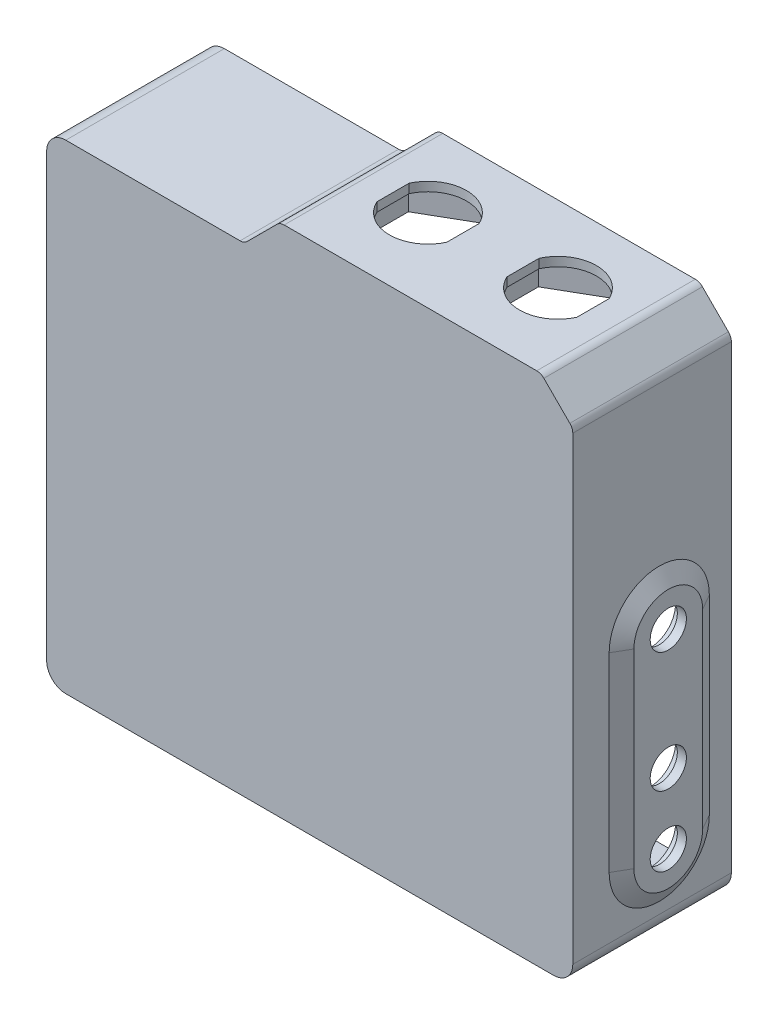
SolidWorks part; units mm, degrees
ref_plane "Front Plane" through (0, 0, 0) normal (0, 0, 1) x (1, 0, 0)
ref_plane "Top Plane" through (0, 0, 0) normal (0, 1, 0) x (1, 0, 0)
ref_plane "Right Plane" through (0, 0, 0) normal (1, 0, 0) x (0, 0, -1)
sketch "Sketch1" plane through (0, 0, 0) normal (0, 0, 1) x (1, 0, 0)
  line L9 (-68.5151, 31.874) -> (-68.5151, -49.766)
  line L10 (-31.5951, 31.874) -> (22.4049, 31.874)
  line L11 (22.4049, 31.874) -> (22.4049, -31.776)
  line L12 (22.4049, -31.776) -> (22.4049, -46.156)
  line L13 (22.4049, -46.156) -> (22.4049, -49.766)
  line L14 (-31.5951, -49.766) -> (-68.5151, -49.766)
  line L15 (22.4049, -49.766) -> (-31.5951, -49.766)
  line L16 (-31.5951, 36.874) -> (25.4049, 36.874)
  line L17 (-68.5151, 31.874) -> (-31.5951, 31.874)
  line L18 (27.4049, 34.874) -> (27.4049, -31.776)
  line L19 (27.4049, -31.776) -> (27.4049, -46.156)
  line L20 (27.4049, -46.156) -> (27.4049, -52.766)
  line L21 (25.4049, -54.766) -> (-31.5951, -54.766)
  line L22 (-31.5951, -54.766) -> (-71.5151, -54.766)
  line L23 (-73.5151, 34.874) -> (-73.5151, -52.766)
  line L24 (-71.5151, 36.874) -> (-31.5951, 36.874)
  line L25 (-31.5951, 36.874) -> (27.4049, 36.874) construction
  line L26 (27.4049, 36.874) -> (27.4049, -31.776) construction
  line L27 (27.4049, -46.156) -> (27.4049, -54.766) construction
  line L28 (27.4049, -54.766) -> (-31.5951, -54.766) construction
  line L29 (-31.5951, -54.766) -> (-73.5151, -54.766) construction
  line L30 (-73.5151, 36.874) -> (-73.5151, -54.766) construction
  line L31 (-73.5151, 36.874) -> (-31.5951, 36.874) construction
  line L32 (-71.5151, 38.674) -> (-31.5951, 38.674)
  line L33 (-31.5951, 38.674) -> (25.4049, 38.674)
  line L34 (29.2049, 34.874) -> (29.2049, -31.776)
  line L35 (29.2049, -31.776) -> (29.2049, -46.156)
  line L36 (29.2049, -46.156) -> (29.2049, -52.766)
  line L37 (25.4049, -56.566) -> (-31.5951, -56.566)
  line L38 (-31.5951, -56.566) -> (-71.5151, -56.566)
  line L39 (-75.3151, 34.874) -> (-75.3151, -52.766)
  arc A0 (25.4049, 36.874) -> (27.4049, 34.874) centre (25.4049, 34.874) cw
  arc A1 (27.4049, -52.766) -> (25.4049, -54.766) centre (25.4049, -52.766) cw
  arc A2 (-71.5151, -54.766) -> (-73.5151, -52.766) centre (-71.5151, -52.766) cw
  arc A3 (-73.5151, 34.874) -> (-71.5151, 36.874) centre (-71.5151, 34.874) cw
  arc A4 (25.4049, 38.674) -> (29.2049, 34.874) centre (25.4049, 34.874) cw
  arc A5 (29.2049, -52.766) -> (25.4049, -56.566) centre (25.4049, -52.766) cw
  arc A6 (-71.5151, -56.566) -> (-75.3151, -52.766) centre (-71.5151, -52.766) cw
  arc A7 (-75.3151, 34.874) -> (-71.5151, 38.674) centre (-71.5151, 34.874) cw
  dimension "D2" = 2
  dimension "D1" = 5
  dimension "D3" = 1.8
extrude "Boss-Extrude1" add sketch "Sketch1" along normal blind 1.5 contours L32 L33 A4 L34 L35 L36 A5 L37 L38 A6 L39 A7
sketch "Sketch2" plane through (0, 0, 1.5) normal (0, 0, 1) x (1, 0, 0)
  line L9 (-22.7084, 43.974) -> (-22.7084, 50.974)
  line L10 (-9.2084, 43.974) -> (-9.2084, 50.974)
  line L11 (3.1216, 43.974) -> (3.1216, 50.974)
  line L12 (16.6216, 43.974) -> (16.6216, 50.974)
  line L13 (18.8716, 41.674) -> (18.8716, 38.674)
  line L14 (0.8716, 41.674) -> (0.8716, 38.674)
  line L15 (-6.9584, 41.674) -> (-6.9584, 38.674)
  line L16 (-24.9584, 41.674) -> (-24.9584, 38.674)
  line L17 (-71.5151, 38.674) -> (25.4049, 38.674)
  line L18 (-22.7084, 43.974) -> (-24.9584, 43.974)
  line L19 (-24.9584, 43.974) -> (-24.9584, 41.674)
  line L20 (-9.2084, 43.974) -> (-6.9584, 43.974)
  line L21 (-6.9584, 43.974) -> (-6.9584, 41.674)
  line L22 (3.1216, 43.974) -> (0.8716, 43.974)
  line L23 (0.8716, 43.974) -> (0.8716, 41.674)
  line L24 (16.6216, 43.974) -> (18.8716, 43.974)
  line L25 (18.8716, 43.974) -> (18.8716, 41.674)
  line L26 (-22.7084, 45.774) -> (-24.9584, 45.774)
  line L27 (-9.2084, 45.774) -> (-6.9584, 45.774)
  line L28 (3.1216, 45.774) -> (0.8716, 45.774)
  line L29 (16.6216, 45.774) -> (18.8716, 45.774)
  line L30 (-24.9584, 45.774) -> (-28.9584, 45.774)
  line L31 (-28.9584, 45.774) -> (-36.0584, 38.674)
  line L32 (18.8716, 45.774) -> (22.8716, 45.774)
  line L33 (29.2049, 34.874) -> (29.2049, -52.766) construction
  line L34 (29.2049, 34.874) -> (29.2049, -52.766)
  line L35 (29.2049, 34.874) -> (29.2049, 39.4408)
  line L36 (-22.7084, 45.774) -> (-9.2084, 45.774)
  line L37 (22.8716, 45.774) -> (29.2049, 39.4408)
  line L38 (-6.9584, 45.774) -> (0.8716, 45.774)
  line L39 (3.1216, 45.774) -> (16.6216, 45.774)
  arc M10 (29.2049, 34.874) -> (25.4049, 38.674) centre (25.4049, 34.874) ccw
  line M11 (25.4049, 38.674) -> (-71.5151, 38.674)
  dimension "D1" = 1.8
  dimension "D2" = 1.8
  dimension "D3" = 1.8
  dimension "D4" = 1.8
extrude "Boss-Extrude2" add sketch "Sketch2" against normal blind 1.5 separate body contours L30 L31 L16 L19 L18 L9 L26 M11 | L36 L9 L18 L19 L16 L15 L21 L20 L10 M11 | L38 L27 L10 L20 L21 L15 L14 L23 L22 L11 L28 M11 | L39 L11 L22 L23 L14 L13 L25 L24 L12 M11 | L37 L32 L29 L12 L24 L25 L13 L35 M11 M10 region at (-28.6478, 41.8928, 1.5) region at (-15.9584, 42.0447, 1.5) region at (-3.0434, 42.561, 1.5) region at (9.8716, 42.0447, 1.5) region at (22.8246, 41.6987, 1.5)
fillet "Fillet1" radius 2 4 edges at (22.8716, 45.774, 0.75) (29.2049, 39.4408, 0.75) (-28.9584, 45.774, 0.75) (-36.0584, 38.674, 0.75)
sketch "Sketch3" plane through (0, 0, 0) normal (0, 0, -1) x (-1, 0, 0)
  line L0 (-29.2049, 38.6123) -> (-29.2049, -52.766) construction
  line L1 (-23.4574, 45.1882) -> (-28.6191, 40.0265) construction
  line L2 (-22.0432, 45.774) -> (28.1299, 45.774) construction
  line L3 (29.5442, 45.1882) -> (35.4726, 39.2598) construction
  line L4 (71.5151, 38.674) -> (36.8868, 38.674) construction
  line L5 (75.3151, 34.874) -> (75.3151, -52.766) construction
  line L6 (-25.4049, -56.566) -> (71.5151, -56.566) construction
  line L7 (-29.2049, 38.6123) -> (-29.2049, -52.766)
  line L8 (-23.4574, 45.1882) -> (-28.6191, 40.0265)
  line L9 (-22.0432, 45.774) -> (28.1299, 45.774)
  line L10 (29.5442, 45.1882) -> (35.4726, 39.2598)
  line L11 (71.5151, 38.674) -> (36.8868, 38.674)
  line L12 (75.3151, 34.874) -> (75.3151, -52.766)
  line L13 (-25.4049, -56.566) -> (71.5151, -56.566)
  line L14 (-25.4049, -54.766) -> (71.5151, -54.766)
  line L15 (73.5151, 34.874) -> (73.5151, -52.766)
  line L16 (71.5151, 36.874) -> (36.8868, 36.874)
  line L17 (28.2714, 43.9154) -> (34.1998, 37.987)
  line L18 (-22.0432, 43.974) -> (28.1299, 43.974)
  line L19 (-22.1846, 43.9154) -> (-27.3463, 38.7538)
  line L20 (-27.4049, 38.6123) -> (-27.4049, -52.766)
  arc A0 (-29.2049, -52.766) -> (-25.4049, -56.566) centre (-25.4049, -52.766) ccw construction
  arc A1 (-28.6191, 40.0265) -> (-29.2049, 38.6123) centre (-27.2049, 38.6123) ccw construction
  arc A2 (-22.0432, 45.774) -> (-23.4574, 45.1882) centre (-22.0432, 43.774) ccw construction
  arc A3 (29.5442, 45.1882) -> (28.1299, 45.774) centre (28.1299, 43.774) ccw construction
  arc A4 (35.4726, 39.2598) -> (36.8868, 38.674) centre (36.8868, 40.674) ccw construction
  arc A5 (75.3151, 34.874) -> (71.5151, 38.674) centre (71.5151, 34.874) ccw construction
  arc A6 (71.5151, -56.566) -> (75.3151, -52.766) centre (71.5151, -52.766) ccw construction
  arc A7 (-29.2049, -52.766) -> (-25.4049, -56.566) centre (-25.4049, -52.766) ccw
  arc A8 (-28.6191, 40.0265) -> (-29.2049, 38.6123) centre (-27.2049, 38.6123) ccw
  arc A9 (-22.0432, 45.774) -> (-23.4574, 45.1882) centre (-22.0432, 43.774) ccw
  arc A10 (29.5442, 45.1882) -> (28.1299, 45.774) centre (28.1299, 43.774) ccw
  arc A11 (35.4726, 39.2598) -> (36.8868, 38.674) centre (36.8868, 40.674) ccw
  arc A12 (75.3151, 34.874) -> (71.5151, 38.674) centre (71.5151, 34.874) ccw
  arc A13 (71.5151, -56.566) -> (75.3151, -52.766) centre (71.5151, -52.766) ccw
  arc A14 (71.5151, -54.766) -> (73.5151, -52.766) centre (71.5151, -52.766) ccw
  arc A15 (73.5151, 34.874) -> (71.5151, 36.874) centre (71.5151, 34.874) ccw
  arc A16 (34.1998, 37.987) -> (36.8868, 36.874) centre (36.8868, 40.674) ccw
  arc A17 (28.2714, 43.9154) -> (28.1299, 43.974) centre (28.1299, 43.774) ccw
  arc A18 (-22.0432, 43.974) -> (-22.1846, 43.9154) centre (-22.0432, 43.774) ccw
  arc A19 (-27.3463, 38.7538) -> (-27.4049, 38.6123) centre (-27.2049, 38.6123) ccw
  arc A20 (-27.4049, -52.766) -> (-25.4049, -54.766) centre (-25.4049, -52.766) ccw
  line M2 (28.1299, 45.774) -> (-22.0432, 45.774)
  arc M3 (-22.0432, 45.774) -> (-23.4574, 45.1882) centre (-22.0432, 43.774) ccw
  line M4 (-23.4574, 45.1882) -> (-28.6191, 40.0265)
  arc M5 (-28.6191, 40.0265) -> (-29.2049, 38.6123) centre (-27.2049, 38.6123) ccw
  line M6 (-29.2049, 38.6123) -> (-29.2049, -52.766)
  arc M7 (-29.2049, -52.766) -> (-25.4049, -56.566) centre (-25.4049, -52.766) ccw
  line M8 (-25.4049, -56.566) -> (71.5151, -56.566)
  arc M9 (71.5151, -56.566) -> (75.3151, -52.766) centre (71.5151, -52.766) ccw
  line M10 (75.3151, -52.766) -> (75.3151, 34.874)
  arc M11 (75.3151, 34.874) -> (71.5151, 38.674) centre (71.5151, 34.874) ccw
  line M12 (71.5151, 38.674) -> (36.8868, 38.674)
  arc M13 (36.8868, 38.674) -> (35.4726, 39.2598) centre (36.8868, 40.674) cw
  line M14 (35.4726, 39.2598) -> (29.5442, 45.1882)
  arc M15 (29.5442, 45.1882) -> (28.1299, 45.774) centre (28.1299, 43.774) ccw
  dimension "D1" = 1.8
extrude "Boss-Extrude3" add sketch "Sketch3" along normal blind 30 contours A20 L20 A19 L19 A18 L18 A17 L17 A16 L16 A15 L15 A14 L14 M15 M2 M3 M4 M5 M6 M7 M8 M9 M10 M11 M12 M13 M14 region at (27.7012, 38.8179, 0)
sketch "Sketch5" plane through (29.2049, 0, 0) normal (1, 0, 0) x (0, 0, -1)
  line L4 (-1.5, -52.766) -> (30, -52.766)
  line L5 (30, -52.766) -> (30, 38.6123)
  line L6 (30, 38.6123) -> (-1.5, 38.6123)
  line L7 (-1.5, 38.6123) -> (-1.5, -52.766)
  line L8 (-1.5, -52.766) -> (30, -52.766)
  line L9 (30, -52.766) -> (30, 38.6123)
  line L10 (30, 38.6123) -> (-1.5, 38.6123)
  line L11 (-1.5, 38.6123) -> (-1.5, -52.766)
  circle A1 centre (15.675, -40.576) radius 4.832
  circle A3 centre (15.675, -26.676) radius 4.832
  circle A5 centre (15.675, -2.776) radius 4.832
  circle A6 centre (15.675, -40.576) radius 5.032
  circle A7 centre (15.675, -26.676) radius 5.032
  circle A8 centre (15.675, -2.776) radius 5.032
  dimension "D1" = 0
  dimension "D2" = 0.2
extrude "Cut-Extrude1" cut sketch "Sketch5" against normal blind 10 contours A6 A1 | A1 | A7 A3 | A3 | A8 A5 | A5 region at (29.2049, -40.576, -15.675) region at (29.2049, -26.676, -15.675) region at (29.2049, -2.776, -15.675) region at (29.2049, -40.576, -10.7853) region at (29.2049, -26.676, -10.7853) region at (29.2049, -2.776, -10.7853)
sketch "Sketch6" plane through (29.2049, 0, 0) normal (1, 0, 0) x (0, 0, -1)
  line L2 (8.843, -40.576) -> (8.843, -2.776)
  line L3 (22.507, -40.576) -> (22.507, -2.776)
  circle A0 centre (15.675, -2.776) radius 5.032 construction
  circle A1 centre (15.675, -40.576) radius 5.032 construction
  circle A2 centre (15.675, -40.576) radius 3.597
  circle A3 centre (15.675, -26.676) radius 3.597
  arc A4 (22.507, -2.776) -> (8.843, -2.776) centre (15.675, -2.776) ccw
  arc A5 (8.843, -40.576) -> (22.507, -40.576) centre (15.675, -40.576) ccw
  arc A7 (20.707, -2.776) -> (10.643, -2.776) centre (15.675, -2.776) ccw
  circle A8 centre (15.675, -2.776) radius 3.597
  arc A9 (10.643, -40.576) -> (20.707, -40.576) centre (15.675, -40.576) ccw
  circle A15 centre (15.675, -2.776) radius 3.397
  circle A16 centre (15.675, -26.676) radius 3.397
  circle A17 centre (15.675, -40.576) radius 3.397
  circle M3 centre (15.675, -26.676) radius 5.032
  circle M4 centre (15.675, -2.776) radius 5.032
  circle M5 centre (15.675, -40.576) radius 5.032
  dimension "D1" = 0.2
extrude "Boss-Extrude4" add sketch "Sketch6" along normal blind 1.8 contours L2 A5 L3 A4 M3 M5 M4 | A2 M5 | A8 M4 | A3 M3 region at (29.2049, -20.739, -15.675) region at (29.2049, -7.6657, -15.675) region at (29.2049, -35.6863, -15.675) region at (29.2049, -26.676, -10.7853)
chamfer "Chamfer1" distance 1.8 angle 60 4 edges at (29.2049, -21.676, -8.843) (29.2049, -47.408, -15.675) (29.2049, 4.056, -15.675) (29.2049, -21.676, -22.507) first distance on face at (30.1049, -21.676, -8.843) first distance on face at (30.1049, -43.992, -15.675) first distance on face at (30.1049, 0.64, -15.675) first distance on face at (30.1049, -21.676, -22.507)
sketch "Sketch7" plane through (0, 45.774, 0) normal (0, 1, 0) x (1, 0, 0)
  line L8 (3.1216, 14.8923) -> (3.1216, 11.7395)
  line L9 (3.1216, 14.8923) -> (3.1216, 18.0451)
  line L10 (16.6216, 14.8923) -> (16.6216, 11.7395)
  line L11 (16.6216, 14.8923) -> (16.6216, 18.0451)
  line L12 (-9.2084, 14.8923) -> (-9.2084, 11.7395)
  line L13 (-9.2084, 14.8923) -> (-9.2084, 18.0451)
  line L14 (-22.7084, 14.8923) -> (-22.7084, 11.7395)
  line L15 (-22.7084, 14.8923) -> (-22.7084, 18.0451)
  line L16 (-22.9084, 14.8923) -> (-22.9084, 18.0892)
  line L17 (-22.9084, 14.8923) -> (-22.9084, 11.6954)
  line L18 (-9.0084, 14.8923) -> (-9.0084, 11.6954)
  line L19 (-9.0084, 14.8923) -> (-9.0084, 18.0892)
  line L20 (2.9216, 14.8923) -> (2.9216, 18.0892)
  line L21 (2.9216, 14.8923) -> (2.9216, 11.6954)
  line L22 (16.8216, 14.8923) -> (16.8216, 11.6954)
  line L23 (16.8216, 14.8923) -> (16.8216, 18.0892)
  arc A4 (3.1216, 11.7395) -> (16.6216, 11.7395) centre (9.8716, 14.8923) ccw
  arc A5 (16.6216, 18.0451) -> (3.1216, 18.0451) centre (9.8716, 14.8923) ccw
  arc A6 (-22.7084, 11.7395) -> (-9.2084, 11.7395) centre (-15.9584, 14.8923) ccw
  arc A7 (-9.2084, 18.0451) -> (-22.7084, 18.0451) centre (-15.9584, 14.8923) ccw
  arc A8 (-9.0084, 18.0892) -> (-22.9084, 18.0892) centre (-15.9584, 14.8923) ccw
  arc A9 (-22.9084, 11.6954) -> (-9.0084, 11.6954) centre (-15.9584, 14.8923) ccw
  arc A10 (16.8216, 18.0892) -> (2.9216, 18.0892) centre (9.8716, 14.8923) ccw
  arc A11 (2.9216, 11.6954) -> (16.8216, 11.6954) centre (9.8716, 14.8923) ccw
  dimension "D1" = 0.2
extrude "Cut-Extrude2" cut sketch "Sketch7" against normal blind 11.8 contours L17 A9 L18 L19 A8 L16 A7 L13 L12 A6 L14 L15 | L13 A7 L15 L14 A6 L12 | L21 A11 L22 L23 A10 L20 A5 L11 L10 A4 L8 L9 | L11 A5 L9 L8 A4 L10 region at (9.8716, 45.774, -14.8923) region at (-15.9584, 45.774, -14.8923) region at (-22.8877, 45.774, -16.4907) region at (2.9423, 45.774, -16.4907)
sketch "Sketch8" plane through (0, 43.974, 0) normal (0, -1, 0) x (1, 0, 0)
  line L14 (-15.9584, -4.5) -> (-24.9584, -9.6962)
  line L15 (-24.9584, -9.6962) -> (-24.9584, -20.0885)
  line L16 (-24.9584, -20.0885) -> (-15.9584, -25.2846)
  line L17 (-15.9584, -25.2846) -> (-6.9584, -20.0885)
  line L18 (-6.9584, -20.0885) -> (-6.9584, -9.6962)
  line L19 (-6.9584, -9.6962) -> (-15.9584, -4.5)
  line L20 (9.8716, -4.5) -> (0.8716, -9.6962)
  line L21 (0.8716, -9.6962) -> (0.8716, -20.0885)
  line L22 (0.8716, -20.0885) -> (9.8716, -25.2846)
  line L23 (9.8716, -25.2846) -> (18.8716, -20.0885)
  line L24 (18.8716, -20.0885) -> (18.8716, -9.6962)
  line L25 (18.8716, -9.6962) -> (9.8716, -4.5)
  line L26 (-28.1299, -30) -> (-28.1299, 0)
  line L27 (22.0432, -30) -> (22.0432, 0)
  line L28 (22.0432, 0) -> (-28.1299, 0) construction
  line L29 (22.0432, -30) -> (-28.1299, -30) construction
  line L30 (22.0432, 0) -> (-28.1299, 0)
  line L31 (22.0432, -30) -> (-28.1299, -30)
  line L32 (0.6716, -20.2039) -> (9.8716, -25.5155)
  line L33 (9.8716, -25.5155) -> (19.0716, -20.2039)
  line L34 (19.0716, -20.2039) -> (19.0716, -9.5807)
  line L35 (19.0716, -9.5807) -> (9.8716, -4.2691)
  line L36 (9.8716, -4.2691) -> (0.6716, -9.5807)
  line L37 (0.6716, -9.5807) -> (0.6716, -20.2039)
  line L38 (-15.9584, -25.5155) -> (-6.7584, -20.2039)
  line L39 (-6.7584, -20.2039) -> (-6.7584, -9.5807)
  line L40 (-6.7584, -9.5807) -> (-15.9584, -4.2691)
  line L41 (-15.9584, -4.2691) -> (-25.1584, -9.5807)
  line L42 (-25.1584, -9.5807) -> (-25.1584, -20.2039)
  line L43 (-25.1584, -20.2039) -> (-15.9584, -25.5155)
  line M11 (22.0432, 0) -> (-28.1299, 0)
  line M12 (-28.1299, 0) -> (-28.1299, -30)
  line M13 (-28.1299, -30) -> (22.0432, -30)
  line M14 (22.0432, -30) -> (22.0432, 0)
  dimension "D1" = 0.2
extrude "Boss-Extrude5" add sketch "Sketch8" along normal up to surface (5.3 mm away) contours L43 L42 L41 L40 L39 L38 L37 L36 L35 L34 L33 L32 M14 M11 M12 M13 region at (-3.0434, 43.974, -15.0687)
sketch "Sketch9" plane through (0, 0, -30) normal (0, 0, -1) x (-1, 0, 0)
  line L0 (28.2714, 43.9154) -> (34.1998, 37.987) construction
  line L1 (28.1299, 38.674) -> (28.1299, 43.974) construction
  line L2 (-27.4049, 38.6123) -> (-27.4049, -52.766) construction
  line L3 (-22.0432, 38.674) -> (-22.0432, 43.974) construction
  line L4 (-22.1846, 43.9154) -> (-27.3463, 38.7538) construction
  line L5 (28.2714, 43.9154) -> (34.1998, 37.987)
  line L6 (28.1299, 38.674) -> (28.1299, 43.974)
  line L7 (-27.4049, 38.6123) -> (-27.4049, -52.766)
  line L8 (-22.0432, 38.674) -> (-22.0432, 43.974)
  line L9 (-22.1846, 43.9154) -> (-27.3463, 38.7538)
  line L10 (-22.0432, 38.674) -> (-27.3951, 38.674)
  line L11 (28.1299, 38.674) -> (33.5128, 38.674)
  arc A0 (34.1998, 37.987) -> (36.8868, 36.874) centre (36.8868, 40.674) ccw construction
  arc A1 (34.1998, 37.987) -> (36.8868, 36.874) centre (36.8868, 40.674) ccw
  arc A2 (-27.3463, 38.7538) -> (-27.4049, 38.6123) centre (-27.2049, 38.6123) ccw construction
  arc M3 (-27.4049, 38.6123) -> (-27.3463, 38.7538) centre (-27.2049, 38.6123) cw
  line M4 (-27.3463, 38.7538) -> (-22.1846, 43.9154)
  arc M5 (-22.1846, 43.9154) -> (-22.0432, 43.974) centre (-22.0432, 43.774) cw
  line M6 (-22.0432, 43.974) -> (-22.0432, 38.674)
  line M8 (28.1299, 38.674) -> (28.1299, 43.974)
  arc M9 (28.1299, 43.974) -> (28.2714, 43.9154) centre (28.1299, 43.774) cw
  line M10 (28.2714, 43.9154) -> (34.1998, 37.987)
extrude "Boss-Extrude6" add sketch "Sketch9" against normal up to surface (30 mm away) separate body contours L10 M6 M5 M4 M3 | L11 M8 M10 M9 region at (-29.9247, 40.4672, -30) region at (23.8378, 40.4673, -30) up to face at (-17.0085, 16.3369, 0)
fillet "Fillet2" radius 2 2 edges at (-33.5128, 38.674, -15) (27.3951, 38.674, -15)
sketch "Sketch10" plane through (0, 0, 0) normal (0, 0, -1) x (-1, 0, 0)
  circle A16 centre (65.0151, 9.644) radius 1.5
  circle A17 centre (35.6451, -31.586) radius 1.5
  circle A18 centre (35.6451, -3.706) radius 1.5
  circle A19 centre (35.6451, 24.174) radius 1.5
  circle A20 centre (25.9851, -46.156) radius 1.5
  circle A21 centre (-18.7949, -46.156) radius 1.5
  circle A22 centre (-18.7949, -31.776) radius 1.5
  circle A23 centre (25.9851, -31.776) radius 1.5
  circle A24 centre (25.9851, -22.556) radius 1.5
  circle A25 centre (25.9851, -8.176) radius 1.5
  circle A26 centre (-18.7949, -22.556) radius 1.5
  circle A27 centre (-18.7949, -8.176) radius 1.5
  circle A28 centre (-18.7949, 1.044) radius 1.5
  circle A29 centre (25.9851, 1.044) radius 1.5
  circle A30 centre (25.9851, 15.424) radius 1.5
  circle A31 centre (-18.7949, 15.424) radius 1.5
  circle A34 centre (65.0151, -46.116) radius 1.5
  circle A35 centre (65.0151, -18.236) radius 1.5
  circle A36 centre (-18.7949, 15.424) radius 2.85
  circle A37 centre (25.9851, 15.424) radius 2.85
  circle A38 centre (25.9851, 1.044) radius 2.85
  circle A39 centre (-18.7949, 1.044) radius 2.85
  circle A40 centre (-18.7949, -8.176) radius 2.85
  circle A41 centre (25.9851, -8.176) radius 2.85
  circle A42 centre (25.9851, -22.556) radius 2.85
  circle A43 centre (-18.7949, -22.556) radius 2.85
  circle A44 centre (-18.7949, -31.776) radius 2.85
  circle A45 centre (25.9851, -31.776) radius 2.85
  circle A46 centre (25.9851, -46.156) radius 2.85
  circle A47 centre (-18.7949, -46.156) radius 2.85
  circle A48 centre (35.6451, -3.706) radius 2.85
  circle A49 centre (35.6451, 24.174) radius 2.85
  circle A50 centre (65.0151, 9.644) radius 2.85
  circle A51 centre (65.0151, -18.236) radius 2.85
  circle A52 centre (35.6451, -31.586) radius 2.85
  circle A53 centre (65.0151, -46.116) radius 2.85
  dimension "D1" = 1.35
extrude "Boss-Extrude7" add sketch "Sketch10" along normal up to surface (9 mm away)
chamfer "Chamfer2" distance 2 angle 45 18 edges at (-67.8651, -46.116, 0) (-67.8651, -18.236, 0) (-67.8651, 9.644, 0) (-38.4951, -31.586, 0) (-38.4951, -3.706, 0) (-38.4951, 24.174, 0) (-28.8351, -46.156, 0) (15.9449, -46.156, 0) (15.9449, -31.776, 0) (-28.8351, -31.776, 0) (-28.8351, -22.556, 0) (15.9449, -22.556, 0) (15.9449, -8.176, 0) (-28.8351, -8.176, 0) (-28.8351, 1.044, 0) (-28.8351, 15.424, 0) (15.9449, 1.044, 0) (15.9449, 15.424, 0)
sketch "Sketch11" plane through (0, 0, 0) normal (0, 0, -1) x (-1, 0, 0)
  line L0 (71.5151, 36.874) -> (36.8868, 36.874) construction
  line L1 (73.5151, 34.874) -> (73.5151, -52.766) construction
  line L2 (-25.4049, -54.766) -> (71.5151, -54.766) construction
  line L3 (-27.4049, 36.674) -> (-27.4049, -52.766) construction
  line L4 (-25.4049, 38.674) -> (32.6844, 38.674) construction
  line L5 (71.5151, 36.874) -> (36.8868, 36.874)
  line L6 (73.5151, 34.874) -> (73.5151, -52.766)
  line L7 (-25.4049, -54.766) -> (71.5151, -54.766)
  line L8 (-27.4049, 36.674) -> (-27.4049, -52.766)
  line L9 (-25.4049, 38.674) -> (32.6844, 38.674)
  arc A0 (34.0986, 38.0882) -> (32.6844, 38.674) centre (32.6844, 36.674) ccw construction
  arc A1 (34.1998, 37.987) -> (36.8868, 36.874) centre (36.8868, 40.674) ccw construction
  arc A2 (73.5151, 34.874) -> (71.5151, 36.874) centre (71.5151, 34.874) ccw construction
  arc A3 (71.5151, -54.766) -> (73.5151, -52.766) centre (71.5151, -52.766) ccw construction
  arc A4 (-27.4049, -52.766) -> (-25.4049, -54.766) centre (-25.4049, -52.766) ccw construction
  arc A5 (-25.4049, 38.674) -> (-27.4049, 36.674) centre (-25.4049, 36.674) ccw construction
  arc A6 (34.0986, 38.0882) -> (32.6844, 38.674) centre (32.6844, 36.674) ccw
  arc A7 (34.1998, 37.987) -> (36.8868, 36.874) centre (36.8868, 40.674) ccw
  arc A8 (73.5151, 34.874) -> (71.5151, 36.874) centre (71.5151, 34.874) ccw
  arc A9 (71.5151, -54.766) -> (73.5151, -52.766) centre (71.5151, -52.766) ccw
  arc A10 (-27.4049, -52.766) -> (-25.4049, -54.766) centre (-25.4049, -52.766) ccw
  arc A11 (-25.4049, 38.674) -> (-27.4049, 36.674) centre (-25.4049, 36.674) ccw
  circle A12 centre (-25.4049, -52.766) radius 1.5
  circle A13 centre (71.5151, -52.766) radius 1.5
  circle A14 centre (23.0551, -52.766) radius 1.5
  circle A15 centre (-25.4049, 36.674) radius 1.5
  circle A16 centre (71.5151, 34.874) radius 1.5
  circle A17 centre (32.6844, 36.674) radius 1.5
  circle A18 centre (71.5151, -8.946) radius 1.5
  circle A19 centre (-25.4049, -15.8847) radius 1.5
  circle A20 centre (-25.4049, 36.674) radius 2.85
  circle A21 centre (32.6844, 36.674) radius 2.85
  circle A22 centre (71.5151, 34.874) radius 2.85
  circle A23 centre (71.5151, -8.946) radius 2.85
  circle A24 centre (71.5151, -52.766) radius 2.85
  circle A25 centre (23.0551, -52.766) radius 2.85
  circle A26 centre (-25.4049, -52.766) radius 2.85
  circle A27 centre (-25.4049, -15.8847) radius 2.85
  circle M6 centre (25.9851, -46.156) radius 4.85
  line M28 (34.1998, 37.987) -> (34.0986, 38.0882)
  arc M29 (34.0986, 38.0882) -> (32.6844, 38.674) centre (32.6844, 36.674) ccw
  line M30 (32.6844, 38.674) -> (-25.4049, 38.674)
  arc M31 (-25.4049, 38.674) -> (-27.4049, 36.674) centre (-25.4049, 36.674) ccw
  line M32 (-27.4049, 36.674) -> (-27.4049, -52.766)
  arc M33 (-27.4049, -52.766) -> (-25.4049, -54.766) centre (-25.4049, -52.766) ccw
  line M34 (-25.4049, -54.766) -> (71.5151, -54.766)
  arc M35 (71.5151, -54.766) -> (73.5151, -52.766) centre (71.5151, -52.766) ccw
  line M36 (73.5151, -52.766) -> (73.5151, 34.874)
  arc M37 (73.5151, 34.874) -> (71.5151, 36.874) centre (71.5151, 34.874) ccw
  line M38 (71.5151, 36.874) -> (36.8868, 36.874)
  dimension "D1" = 1.35
  dimension "D2" = 1.35
extrude "Boss-Extrude8" add sketch "Sketch11" along normal up to surface (30 mm away) contours A20 L9 A15 M32 M31 | L9 A20 M32 M31 | A21 A7 A17 M30 M28 M29 | A7 A21 M30 M29 M28 | A22 L6 A16 M38 M37 | L6 A22 M38 M37 | L6 A23 | L6 A23 A18 | L7 A24 M36 M35 | A24 L7 A13 M36 M35 | A25 L7 A14 M6 | L7 A25 | A26 M32 M34 M33 | A26 A12 M34 M32 M33 | A27 A19 M32 | A27 M32 | A25 M6 region at (-72.8809, 36.2397, 0) region at (-70.4999, 36.943, 0) region at (-35.4503, 36.9004, 0) region at (-33.3814, 38.6778, 0) region at (-73.8599, -8.946, 0) region at (-73.4403, -8.946, 0) region at (22.8312, 37.7287, 0) region at (24.3897, 38.743, 0) region at (-74.0804, -51.6921, 0) region at (-73.4466, -51.7508, 0) region at (24.3332, -13.3248, 0) region at (27.7496, -15.8847, 0) region at (-23.0551, -55.1108, 0) region at (-23.0551, -54.6912, 0) region at (24.3308, -50.2004, 0) region at (27.4739, -51.7508, 0) region at (-24.1099, -50.3865, 0) up to face at (-26.8549, 6.9607, -30)
fillet "Fillet3" radius 2 16 edges at (-35.4964, 37.1375, -15) (-30.654, 38.674, -15) (-69.4848, 36.874, -15) (-73.5151, 32.8436, -15) (-73.5151, -10.9764, -15) (-73.5151, -6.9156, -15) (-73.5151, -50.7356, -15) (-69.4848, -54.766, -15) (-21.0248, -54.766, -15) (-25.0855, -54.766, -15) (27.4049, -50.7356, -15) (23.3745, -54.766, -15) (27.4049, -13.8543, -15) (27.4049, -17.9151, -15) (27.4049, 34.6436, -15) (23.3745, 38.674, -15)
